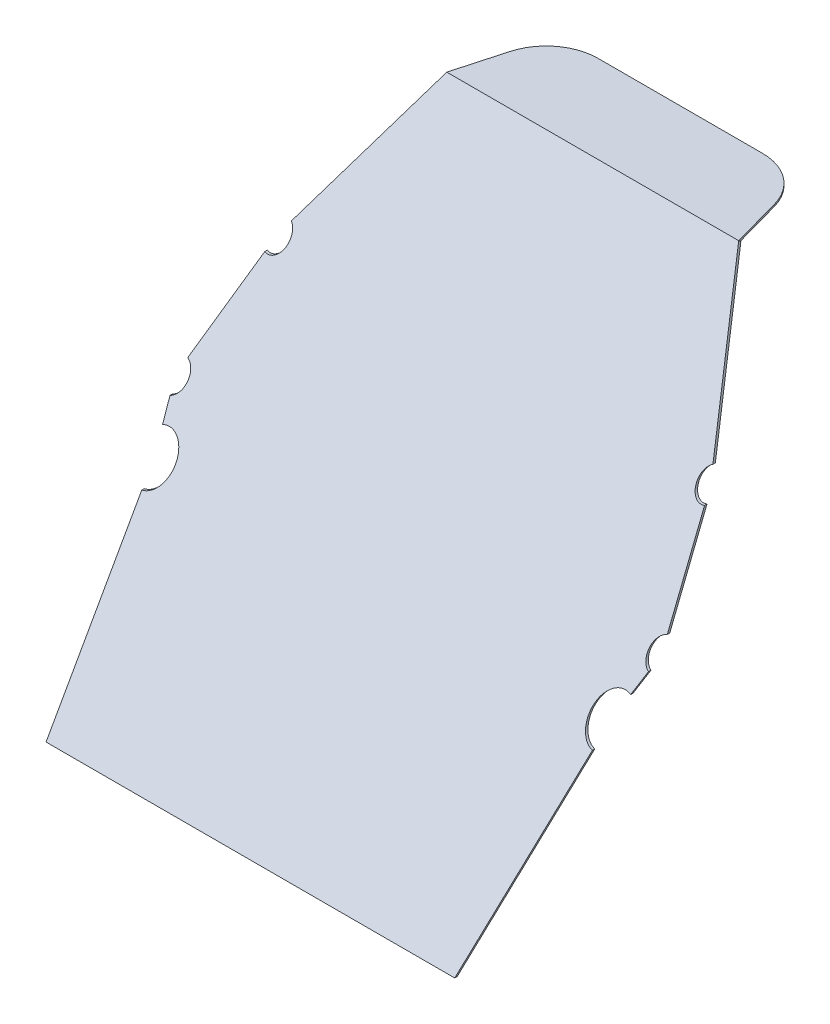
SolidWorks part; units mm, degrees
ref_plane "Front Plane" through (0, 0, 0) normal (0, 0, 1) x (1, 0, 0)
ref_plane "Top Plane" through (0, 0, 0) normal (0, 1, 0) x (1, 0, 0)
ref_plane "Right Plane" through (0, 0, 0) normal (1, 0, 0) x (0, 0, -1)
sketch "Sketch2" plane through (0, 0, 0) normal (0, 1, 0) x (1, 0, 0)
  line L0 (-190.5, 0) -> (190.5, 0)
  line L1 (-107.315, 114.3) -> (107.315, 114.3)
  line L2 (-190.5, 0) -> (-172.5898, 64.65)
  line L3 (190.5, 0) -> (172.5898, 64.65)
  arc A0 (-172.5898, 64.65) -> (-107.315, 114.3) centre (-107.315, 46.5667) cw
  arc A1 (172.5898, 64.65) -> (107.315, 114.3) centre (107.315, 46.5667) ccw
  point P5 (0, 114.3)
  point P10 (73.5943, 210.219)
  point P11 (76.6116, 33.8667)
  dimension "D2" = 67.7333
  dimension "D1" = 381
  dimension "D3" = 114.3
  dimension "D4" = 214.63
extrude "Boss-Extrude1" add sketch "Sketch2" against normal blind 2.54
ref_plane "Plane1" through (0, 0, 0) normal (0, 0.6157, 0.788) x (1, 0, 0)
sketch "Sketch3" plane through (0, 0, 0) normal (0, 0.6157, 0.788) x (1, 0, 0)
  line L0 (-317.5, -1270) -> (317.5, -1270)
  line L2 (317.5, 0) -> (-317.5, 0)
  line L3 (-190.5, 0) -> (190.5, 0) construction
  line L4 (-317.5, 0) -> (-317.5, -1270)
  line L5 (317.5, 0) -> (317.5, -1270)
  point P2 (0, -1270)
  point P9 (0, 0)
  dimension "D1" = 635
  dimension "D2" = 1270
extrude "Boss-Extrude2" add sketch "Sketch3" against normal blind 2.54 contours L4 L0 L5 L2
sketch "Sketch4" plane through (0, 0, 0) normal (0, 0, 1) x (1, 0, 0)
  line L0 (-190.5, 0) -> (190.5, 0) construction
  line L1 (-190.5, 0) -> (190.5, 0)
  line L2 (-266.7, -571.921) -> (266.7, -571.921)
  line L3 (-317.1484, -291.4077) -> (-297.6312, -351.8339)
  line L4 (-317.1484, -291.4077) -> (-282.8177, -165.183)
  line L5 (-282.8177, -165.183) -> (-190.5, 0)
  line L6 (-297.6312, -351.8339) -> (-266.7, -571.921)
  line L7 (-190.5, 0) -> (-571.5, 0)
  line L8 (-571.5, 0) -> (-571.5, -1524)
  line L9 (-571.5, -1524) -> (571.5, -1524)
  line L10 (0, 0) -> (0, 50000) construction
  line L11 (571.5, 0) -> (571.5, -1524)
  line L12 (190.5, 0) -> (571.5, 0)
  line L13 (297.6312, -351.8339) -> (266.7, -571.921)
  line L14 (282.8177, -165.183) -> (190.5, 0)
  line L15 (317.1484, -291.4077) -> (282.8177, -165.183)
  line L16 (317.1484, -291.4077) -> (297.6312, -351.8339)
  circle A0 centre (-297.6312, -351.8339) radius 25.4
  circle A1 centre (-317.1484, -291.4077) radius 15.875
  circle A2 centre (-282.8177, -165.183) radius 15.875
  circle A3 centre (282.8177, -165.183) radius 15.875
  circle A4 centre (317.1484, -291.4077) radius 15.875
  circle A5 centre (297.6312, -351.8339) radius 25.4
  point P4 (0, -571.921)
  point P12 (0, -1524)
  dimension "D11" = 31.75
  dimension "D12" = 50.8
  dimension "D1" = 533.4
  dimension "D2" = 130.81
  dimension "D3" = 222.25
  dimension "D4" = 63.5
  dimension "D5" = 98
  dimension "D6" = 189.23
  dimension "D7" = 119.2
  dimension "D8" = 170.1
  dimension "D9" = 381
  dimension "D10" = 1524
extrude "Cut-Extrude1" cut sketch "Sketch4" along normal through all both and the other way through all contours L10 L9 L11 L12 L14 L15 L16 L13 L2 | L9 L10 L2 L6 L3 L4 L5 L7 L8 | L3 A0 L6 | L6 A0 L3 | L4 A1 L3 | L3 A1 L4 | L5 A2 L4 | L4 A2 L5 | L15 A3 L14 | L14 A3 L15 | L16 A4 L15 | L15 A4 L16 | L13 A5 L16 | L16 A5 L13 region at (0, -866.4692, 0) region at (-276.1048, -167.9236, 0) region at (-288.5627, -162.8376, 0) region at (288.5627, -162.8376, 0) region at (276.1048, -167.9236, 0) region at (-309.2364, -291.2223, 0) region at (-322.6015, -291.5355, 0) region at (322.6015, -291.5355, 0) region at (309.2364, -291.2223, 0) region at (-287.7101, -349.5526, 0) region at (-308.7071, -354.3808, 0) region at (308.7071, -354.3808, 0) region at (287.7101, -349.5526, 0)
